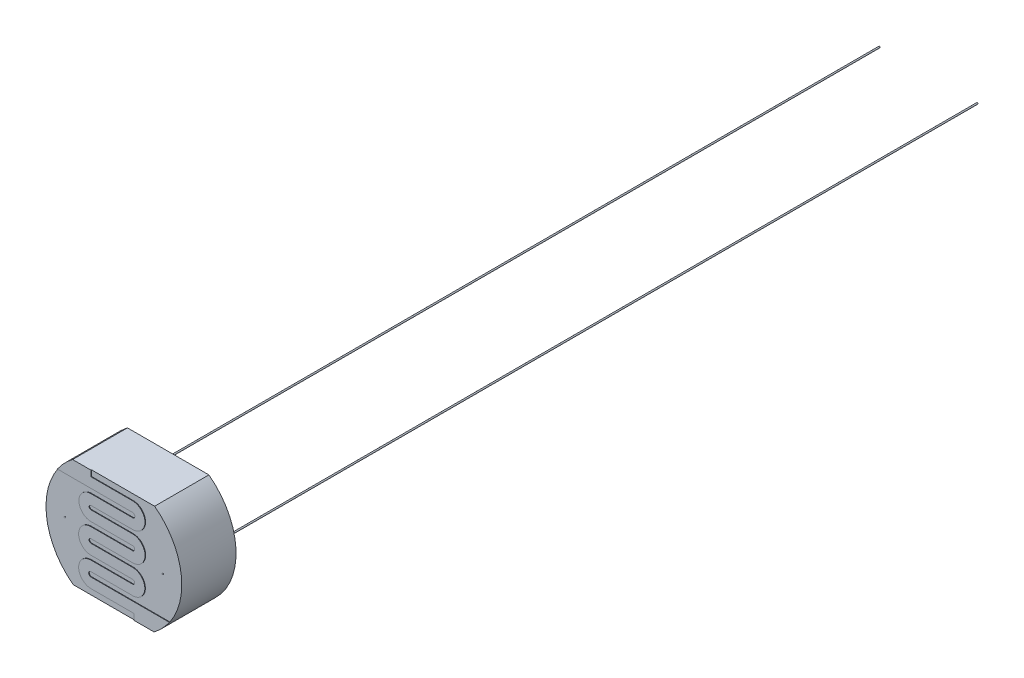
SolidWorks part; units mm, degrees
ref_plane "Alzado" through (0, 0, 0) normal (0, 0, 1) x (1, 0, 0)
ref_plane "Planta" through (0, 0, 0) normal (0, 1, 0) x (1, 0, 0)
ref_plane "Vista lateral" through (0, 0, 0) normal (1, 0, 0) x (0, 0, -1)
sketch "Croquis1" plane through (0, 0, 0) normal (0, 0, 1) x (1, 0, 0)
  line L0 (-1.5, 0) -> (1.5, 0)
  line L1 (-1.5, -4) -> (1.5, -4)
  line L2 (-453.0783, -209.9721) -> (-77.745, -209.9721) construction
  line L3 (-0.8216, -0.2117) -> (0.7082, -0.2117)
  line L4 (-0.8216, -1.1277) -> (0.7082, -1.1277)
  line L5 (0.7082, -0.5831) -> (-0.8216, -0.5831)
  line L6 (0.7648, -4) -> (1.5, -4)
  line L7 (-0.8216, -0.7509) -> (0.7082, -0.7509)
  line L8 (0.7648, -4) -> (1.5, -4)
  line L9 (0.7082, -1.2662) -> (-0.8216, -1.2662)
  line L10 (-0.8216, 0) -> (-1.5, 0)
  line L11 (-0.8216, -1.6416) -> (0.7082, -1.6416)
  line L13 (0.7082, -1.8028) -> (-0.8216, -1.8028)
  line L15 (-0.8216, -2.1883) -> (0.7082, -2.1883)
  line L17 (0.7082, -2.3342) -> (-0.8216, -2.3342)
  line L19 (-0.8216, -2.7153) -> (0.7082, -2.7153)
  line L21 (0.7082, -2.87) -> (-0.8216, -2.87)
  line L23 (-0.8216, -3.238) -> (0.7082, -3.238)
  line L25 (-0.8216, -3.4095) -> (2.0648, -3.4095)
  line L26 (-0.8216, -3.7803) -> (0.7648, -3.7803)
  line L27 (0.7648, -3.7803) -> (0.7648, -4)
  line L28 (-0.8216, -0.2117) -> (-0.8216, 0)
  line L29 (-0.8216, -0.5831) -> (-2.0597, -0.5831)
  arc A0 (1.5, 0) -> (1.5, -4) centre (0, -2) cw
  arc A1 (-1.5, 0) -> (-1.5, -4) centre (0, -2) ccw
  arc A2 (0.7082, -0.2117) -> (0.7082, -1.1277) centre (0.7082, -0.6697) cw
  arc A3 (0.7082, -1.2662) -> (0.7082, -2.1883) centre (0.7082, -1.7272) cw
  arc A4 (0.7082, -2.3342) -> (0.7082, -3.238) centre (0.7082, -2.7861) cw
  arc A5 (-0.8216, -3.7803) -> (-0.8216, -2.87) centre (-0.8216, -3.3251) cw
  arc A6 (-0.8216, -2.7153) -> (-0.8216, -1.8028) centre (-0.8216, -2.259) cw
  arc A7 (-0.8216, -1.6416) -> (-0.8216, -0.7509) centre (-0.8216, -1.1962) cw
  arc A8 (-0.8216, -1.1277) -> (-0.8216, -1.2662) centre (-0.8216, -1.1969) ccw
  arc A9 (-0.8216, -2.1883) -> (-0.8216, -2.3342) centre (-0.8216, -2.2612) ccw
  arc A10 (0.7082, -2.7153) -> (0.7082, -2.87) centre (0.7082, -2.7927) cw
  arc A11 (-0.8216, -3.238) -> (-0.8216, -3.4095) centre (-0.8216, -3.3238) ccw
  arc A12 (0.7082, -1.6416) -> (0.7082, -1.8028) centre (0.7082, -1.7222) cw
  arc A13 (0.7082, -0.5831) -> (0.7082, -0.7509) centre (0.7082, -0.667) cw
  point P4 (0, 0)
  dimension "D3" = 2.5
  dimension "D1" = 3
  dimension "D2" = 4
extrude "Saliente-Extruir3" add sketch "Croquis1" along normal blind 0.02 contours L5 A13 L7 A7 L11 A12 L13 A6 L19 A10 L21 A5 L26 L27 L1 A0 L25 A11 L23 A4 L17 A9 L15 A3 L9 A8 L4 A2 L3 L28 L0 A1 L29 region at (-0.0367, -2.0079, 0)
extrude "Saliente-Extruir5" add sketch "Croquis1<5>" against normal blind 2 contours A13 L5 L29 A1 L1 L27 L26 A5 L21 A10 L19 A6 L13 A12 L11 A7 L7 | L23 A11 L25 A0 L0 L28 L3 A2 L4 A8 L9 A3 L15 A9 L17 A4 | L5 A13 L7 A7 L11 A12 L13 A6 L19 A10 L21 A5 L26 L27 L1 A0 L25 A11 L23 A4 L17 A9 L15 A3 L9 A8 L4 A2 L3 L28 L0 A1 L29 region at (-0.0367, -2.0079, 0) region at (1.3081, -1.7794, 0) region at (-1.3305, -2.222, 0)
sketch "Croquis1<5>" plane through (0, 0, 0) normal (0, 0, 1) x (1, 0, 0) same geometry as "Croquis1"
sketch "Croquis4" plane through (0, 0, 0) normal (0, 0, 1) x (1, 0, 0)
  line L0 (-1.5, -4) -> (0.7648, -4) construction
  line L1 (0.7648, -4) -> (1.5, -4) construction
  circle A0 centre (1.8, -2) radius 0.025
  arc A1 (2.0648, -3.4095) -> (1.5, 0) centre (0, -2) ccw construction
  circle A2 centre (-1.8, -2) radius 0.025
  arc A3 (-2.0597, -0.5831) -> (-1.5, -4) centre (0, -2) ccw construction
  dimension "D1" = 0.05
  dimension "D3" = 0.05
  dimension "D2" = 1.8
  dimension "D4" = 1.8
  dimension "D5" = 2
  dimension "D6" = 2
extrude "Saliente-Extruir6" add sketch "Croquis4" against normal blind 30
extrude "Saliente-Extruir7" add sketch "Croquis4<2>" along normal blind 0.01
sketch "Croquis4<2>" plane through (0, 0, 0) normal (0, 0, 1) x (1, 0, 0) same geometry as "Croquis4"
